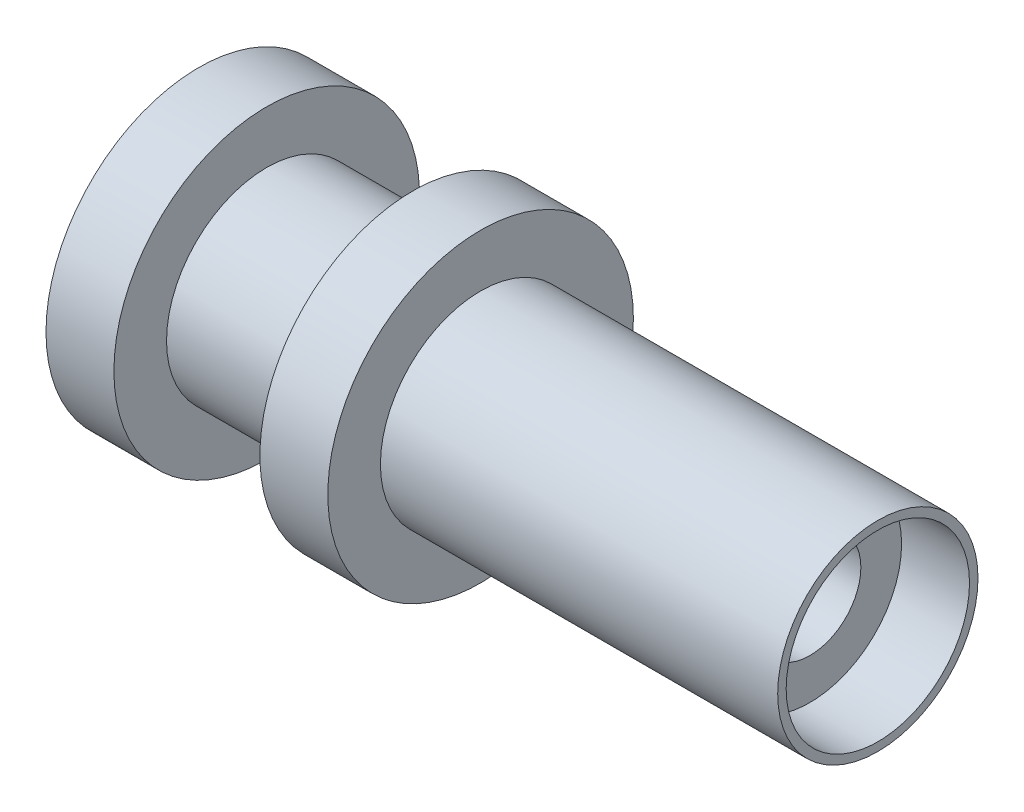
SolidWorks part; units mm, degrees
note: The reader was unsure of these and kept them because the rebuilt part matched: shared geometry of "Sketch4<3>".
ref_plane "Front Plane" through (0, 0, 0) normal (0, 0, 1) x (1, 0, 0)
ref_plane "Top Plane" through (0, 0, 0) normal (0, 1, 0) x (1, 0, 0)
ref_plane "Right Plane" through (0, 0, 0) normal (1, 0, 0) x (0, 0, -1)
sketch "Sketch1" plane through (0, 0, 0) normal (1, 0, 0) x (0, 0, -1)
  circle A0 centre (0, 0) radius 2.95
  dimension "D1" = 5.9
extrude "Boss-Extrude1" add sketch "Sketch1" along normal blind 18
sketch "Sketch2" plane through (18, 0, 0) normal (1, 0, 0) x (0, 0, -1)
  circle A0 centre (0, 0) radius 2.7
  dimension "D1" = 5.4
extrude "Cut-Extrude1" cut sketch "Sketch2" against normal blind 2 contours A0
sketch "Sketch3" plane through (16, 0, 0) normal (1, 0, 0) x (0, 0, -1)
  circle A0 centre (0, 0) radius 1.5
  dimension "D1" = 3
extrude "Cut-Extrude2" cut sketch "Sketch3" against normal through all both and the other way through all
sketch "Sketch4" plane through (0, 0, 0) normal (-1, 0, 0) x (0, 0, 1)
  circle A0 centre (0, 0) radius 4.5
  dimension "D1" = 9
extrude "Boss-Extrude2" add sketch "Sketch4" along normal blind 2 contours A0
extrude "Boss-Extrude3" add sketch "Sketch4<3>" against normal blind 2 from surface at -4.3
sketch "Sketch4<3>" plane through (0, 0, 0) normal (-1, 0, 0) x (0, 0, 1) same geometry as "Sketch4"
sketch "Sketch5" plane through (-2, 0, 0) normal (-1, 0, 0) x (0, 0, 1)
  circle A0 centre (0, 0) radius 1.5
  circle A1 centre (0, 0) radius 4.5 construction
  point P2 (0, 0)
  point P3 (0, 0)
  point P4 (-0.8074, 0.7165)
  dimension "D1" = 3
extrude "Cut-Extrude3" cut sketch "Sketch5" against normal through all both and the other way through all contours A0
sketch "Sketch6" plane through (-2, 0, 0) normal (-1, 0, 0) x (0, 0, 1)
  line L1 (2.75, -1.5877) -> (2.75, 1.5877)
  line L2 (2.75, 1.5877) -> (0, 3.1754)
  line L3 (0, 3.1754) -> (-2.75, 1.5877)
  line L4 (-2.75, 1.5877) -> (-2.75, -1.5877)
  line L5 (-2.75, -1.5877) -> (0, -3.1754)
  line L6 (0, -3.1754) -> (2.75, -1.5877)
  circle A0 centre (0, 0) radius 2.75 construction
  point P1 (0, 0)
  point P9 (0.6862, 0.5863)
  point P11 (0, 0)
  point P12 (2.0602, 2.4164)
  dimension "D1" = 5.5
extrude "Cut-Extrude4" cut sketch "Sketch6" against normal blind 1 and the other way through all contours L1 L2 L3 L4 L5 L6
